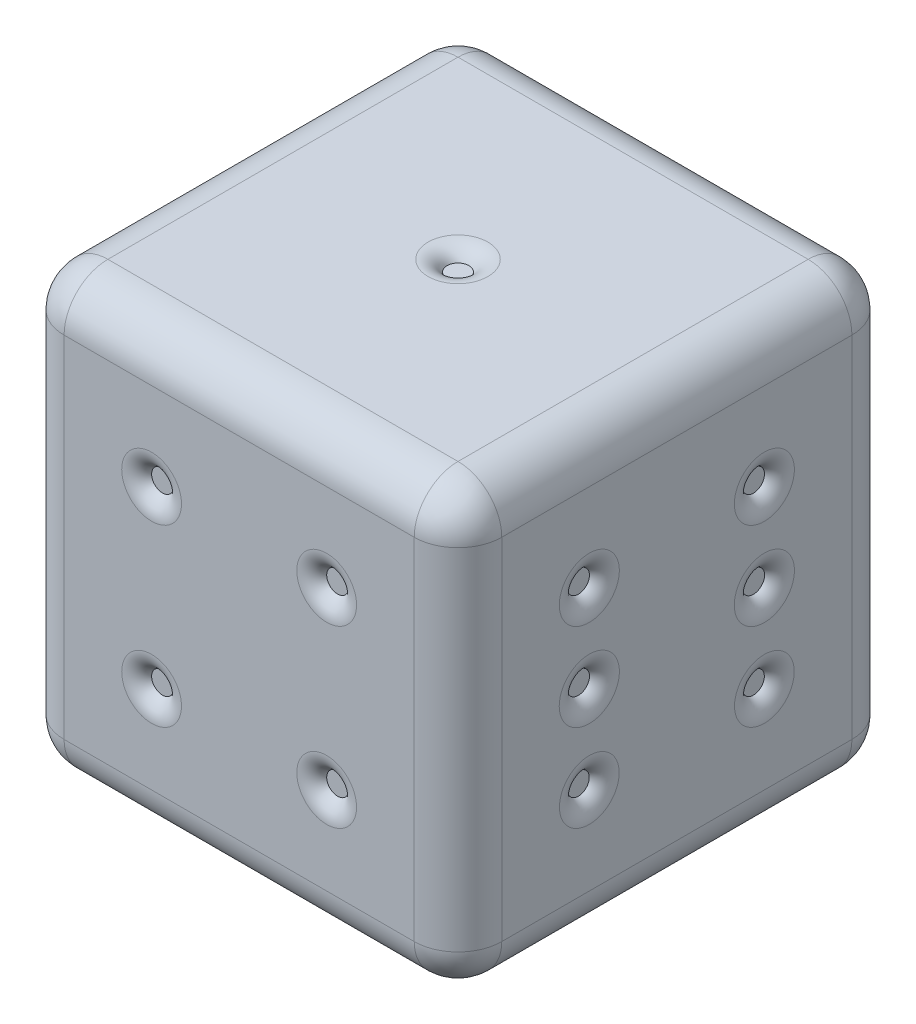
SolidWorks part; units mm, degrees
material "7050-T7451"
ref_plane "Front Plane" through (0, 0, 0) normal (0, 0, 1) x (1, 0, 0)
ref_plane "Top Plane" through (0, 0, 0) normal (0, 1, 0) x (1, 0, 0)
ref_plane "Right Plane" through (0, 0, 0) normal (1, 0, 0) x (0, 0, -1)
sketch "Sketch1" plane through (0, 0, 0) normal (0, 1, 0) x (1, 0, 0)
  line L1 (-5, 5) -> (5, 5)
  line L2 (-5, 5) -> (-5, -5)
  line L3 (-5, -5) -> (5, -5)
  line L4 (5, 5) -> (5, -5)
  line L5 (-5, 5) -> (5, -5) construction
  line L6 (-5, -5) -> (5, 5) construction
  point P0 (0, 0)
  dimension "D1" = 10
  dimension "D2" = 10
extrude "Boss-Extrude1" add sketch "Sketch1" along normal blind 10
fillet "Fillet1" radius 1 12 edges at (5, 5, 5) (0, 0, 5) (5, 0, 0) (0, 0, -5) (5, 5, -5) (0, 10, -5) (5, 10, 0) (0, 10, 5) (-5, 5, -5) (-5, 5, 5) (-5, 0, 0) (-5, 10, 0)
sketch "Sketch3" plane through (0, 10, 0) normal (0, 1, 0) x (1, 0, 0)
  line L0 (4, 0) -> (-4, 0) construction
  line L1 (4, -4) -> (4, 4) construction
  line L2 (-4, 4) -> (-4, -4) construction
  circle A0 centre (0, 0) radius 0.25
extrude "Cut-Extrude2" cut sketch "Sketch3" against normal blind 0.25
fillet "Fillet11" radius 0.5 1 edges at (0, 10, 0.25)
sketch "Sketch4" plane through (-5, 0, 0) normal (-1, 0, 0) x (0, 0, 1)
  line L1 (4, 9) -> (0, 5) construction
  line L2 (0, 5) -> (2, 7) construction
  line L4 (-4, 1) -> (0, 5) construction
  circle A0 centre (2, 7) radius 0.25
  circle A1 centre (-2, 3) radius 0.25
extrude "Cut-Extrude3" cut sketch "Sketch4" against normal blind 0.25
fillet "Fillet12" radius 0.5 2 edges at (-5, 7, 2.25) (-5, 3, -1.75)
sketch "Sketch6" plane through (0, 0, 0) normal (0, -1, 0) x (-1, 0, 0)
  line L0 (-4, 4) -> (0, 0) construction
  line L1 (0, 0) -> (4, -4) construction
  circle A0 centre (0, 0) radius 0.25
  circle A1 centre (2, -2) radius 0.25
  circle A2 centre (-2, 2) radius 0.25
extrude "Cut-Extrude4" cut sketch "Sketch6" against normal blind 0.25
fillet "Fillet13" radius 0.5 3 edges at (-2, 0, 1.75) (0, 0, -0.25) (2, 0, -2.25)
sketch "Sketch10" plane through (5, 0, 0) normal (1, 0, 0) x (0, 0, -1)
  line L0 (0, 1) -> (0, 9) construction
  line L1 (-4, 1) -> (4, 1) construction
  line L2 (4, 9) -> (-4, 9) construction
  line L3 (0, 1) -> (4, 1) construction
  line L4 (2, 1) -> (2, 5) construction
  line L5 (2, 5) -> (2, 9) construction
  line L6 (2, 5) -> (2, 1) construction
  circle A0 centre (2, 3) radius 0.249
  circle A1 centre (2, 5) radius 0.2544
  circle A2 centre (2, 7) radius 0.2526
  circle A3 centre (-2, 7) radius 0.2526
  circle A4 centre (-2, 5) radius 0.2544
  circle A5 centre (-2, 3) radius 0.249
extrude "Cut-Extrude6" cut sketch "Sketch10" against normal blind 0.25
fillet "Fillet15" radius 0.5 3 edges at (5, 7, -2.2526) (5, 5, -2.2544) (5, 3, -2.249)
fillet "Fillet16" radius 0.5 3 edges at (5, 7, 2.2526) (5, 5, 2.2544) (5, 3, 2.249)
sketch "Sketch12" plane through (0, 0, 5) normal (0, 0, 1) x (1, 0, 0)
  line L0 (0, 8.2973) -> (0, 9) construction
  line L1 (4, 9) -> (-4, 9) construction
  line L2 (0, 5) -> (4, 1) construction
  line L3 (-4, 1) -> (4, 1) construction
  line L4 (4, 1) -> (4, 9) construction
  line L5 (4, 1) -> (0, 5) construction
  line L6 (0, 9) -> (0, 1) construction
  line L7 (0, 5) -> (-4, 9) construction
  circle A0 centre (2, 3) radius 0.25
  circle A1 centre (-2, 7) radius 0.25
  circle A2 centre (-2, 3) radius 0.25
  circle A3 centre (2, 7) radius 0.25
extrude "Cut-Extrude7" cut sketch "Sketch12" against normal blind 0.25
fillet "Fillet23" radius 0.5 4 edges at (2.25, 3, 5) (-2.25, 3, 5) (-1.75, 7, 5) (1.75, 7, 5)
mirror "Mirror3" about plane through (0, 0, 0) normal (0, 0, 1) of "Cut-Extrude7"
sketch "Sketch13" plane through (0, 0, -5) normal (0, 0, -1) x (-1, 0, 0)
  line L0 (0, 9) -> (0, 1) construction
  line L1 (4, 9) -> (-4, 9) construction
  line L2 (-4, 1) -> (4, 1) construction
  circle A0 centre (0, 5) radius 0.25
extrude "Cut-Extrude8" cut sketch "Sketch13" against normal blind 0.25
fillet "Fillet24" radius 0.5 5 edges at (2.25, 3, -5) (-2.25, 3, -5) (-1.75, 7, -5) (-0.25, 5, -5) (1.75, 7, -5)
